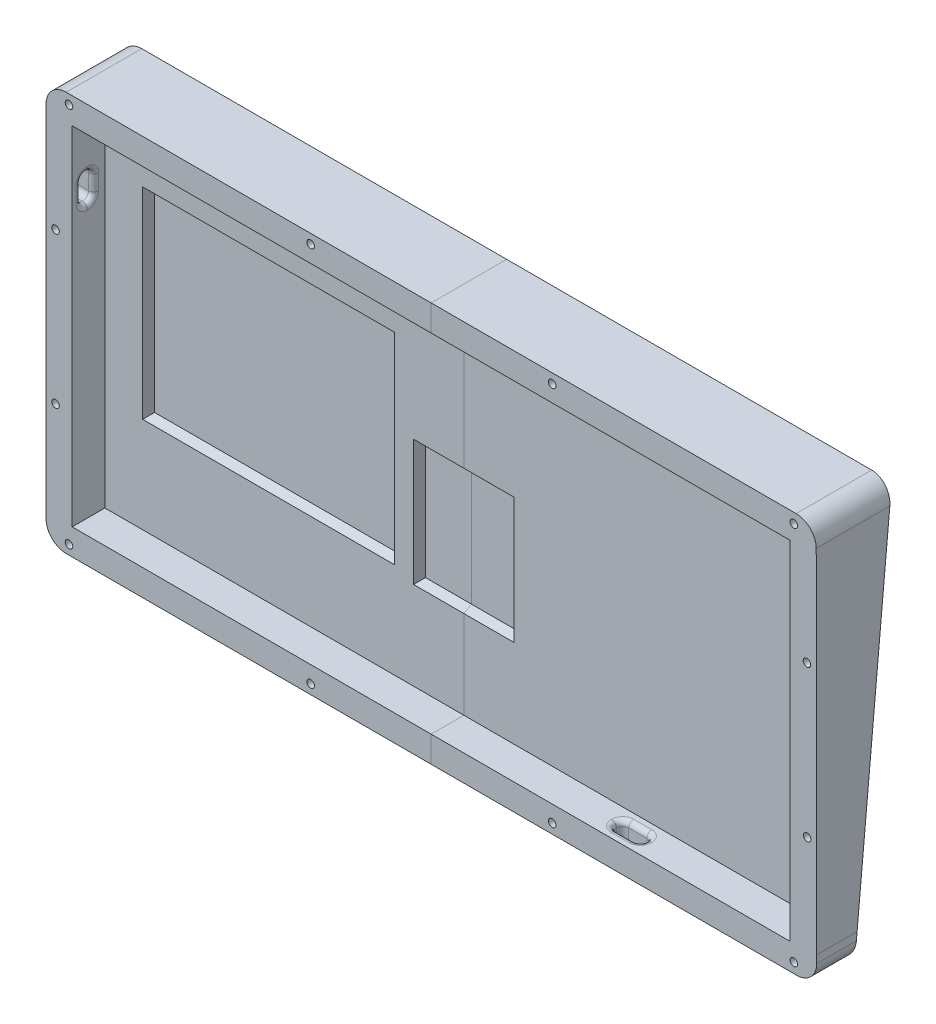
SolidWorks part; units mm, degrees
ref_plane "Front Plane" through (0, 0, 0) normal (0, 0, 1) x (1, 0, 0)
ref_plane "Top Plane" through (0, 0, 0) normal (0, 1, 0) x (1, 0, 0)
ref_plane "Right Plane" through (0, 0, 0) normal (1, 0, 0) x (0, 0, -1)
sketch "Model" plane through (0, 0, 0) normal (0, 0, 1) x (1, 0, 0)
  line L0 (0, 11) -> (0, 150.75)
  line L1 (306.2071, 11.0112) -> (306.0112, 150.7612)
  line L2 (298.0112, 158.75) -> (8, 158.75)
  line L3 (0, 11) -> (0, 8)
  line L4 (8, 0) -> (298.2071, 0)
  line L5 (306.2071, 11.0112) -> (306.2071, 8)
  line L6 (295.63, 10.37) -> (10.37, 10.37)
  line L7 (10.37, 10.37) -> (10.37, 148.38)
  line L8 (10.37, 148.38) -> (295.63, 148.38)
  line L9 (295.63, 148.38) -> (295.63, 10.37)
  arc A0 (8, 158.75) -> (0, 150.75) centre (8, 150.75) ccw
  arc A1 (306.0112, 150.7612) -> (298.0112, 158.75) centre (298.0112, 150.75) ccw
  arc A2 (0, 8) -> (8, 0) centre (8, 8) ccw
  arc A3 (298.2071, 0) -> (306.2071, 8) centre (298.2071, 8) ccw
  circle A4 centre (105.1086, 3.75) radius 1.5
  circle A5 centre (9.1086, 3.75) radius 1.5
  circle A6 centre (201.1085, 3.8173) radius 1.5
  circle A7 centre (297.1084, 3.9518) radius 1.5
  circle A8 centre (105.1086, 155) radius 1.5
  circle A9 centre (9.1086, 155) radius 1.5
  circle A10 centre (201.1085, 154.9327) radius 1.5
  circle A11 centre (297.1084, 154.7982) radius 1.5
  circle A12 centre (3.75, 109.375) radius 1.5
  circle A13 centre (3.75, 49.375) radius 1.5
  circle A14 centre (302.3189, 109.5842) radius 1.5
  circle A15 centre (302.403, 49.5843) radius 1.5
sketch "草图2" plane through (0, 0, 0) normal (0, 0, 1) x (1, 0, 0)
  line L0 (0, 11) -> (0, 150.75)
  line L1 (306.2071, 11.0112) -> (306.0112, 150.7612)
  line L2 (298.0112, 158.75) -> (8, 158.75)
  line L3 (0, 11) -> (0, 8)
  line L4 (8, 0) -> (298.2071, 0)
  line L5 (306.2071, 11.0112) -> (306.2071, 8)
  line L6 (295.63, 10.37) -> (10.37, 10.37)
  line L7 (10.37, 10.37) -> (10.37, 148.38)
  line L8 (10.37, 148.38) -> (295.63, 148.38)
  line L9 (295.63, 148.38) -> (295.63, 10.37)
  arc A0 (8, 158.75) -> (0, 150.75) centre (8, 150.75) ccw
  arc A1 (306.0112, 150.7612) -> (298.0112, 158.75) centre (298.0112, 150.75) ccw
  arc A2 (0, 8) -> (8, 0) centre (8, 8) ccw
  arc A3 (298.2071, 0) -> (306.2071, 8) centre (298.2071, 8) ccw
  circle A4 centre (105.1086, 3.75) radius 1.5
  circle A5 centre (9.1086, 3.75) radius 1.5
  circle A6 centre (201.1085, 3.8173) radius 1.5
  circle A7 centre (297.1084, 3.9518) radius 1.5
  circle A8 centre (105.1086, 155) radius 1.5
  circle A9 centre (9.1086, 155) radius 1.5
  circle A10 centre (201.1085, 154.9327) radius 1.5
  circle A11 centre (297.1084, 154.7982) radius 1.5
  circle A12 centre (3.75, 109.375) radius 1.5
  circle A13 centre (3.75, 49.375) radius 1.5
  circle A14 centre (302.3189, 109.5842) radius 1.5
  circle A15 centre (302.403, 49.5843) radius 1.5
sketch "草图3" plane through (0, 0, 0) normal (0, 0, 1) x (1, 0, 0)
  line L0 (0, 11) -> (0, 150.75)
  line L1 (306.2071, 11.0112) -> (306.0112, 150.7612)
  line L2 (298.0112, 158.75) -> (8, 158.75)
  line L3 (0, 11) -> (0, 8)
  line L4 (8, 0) -> (298.2071, 0)
  line L5 (306.2071, 11.0112) -> (306.2071, 8)
  line L6 (295.63, 10.37) -> (10.37, 10.37)
  line L7 (10.37, 10.37) -> (10.37, 148.38)
  line L8 (10.37, 148.38) -> (295.63, 148.38)
  line L9 (295.63, 148.38) -> (295.63, 10.37)
  arc A0 (8, 158.75) -> (0, 150.75) centre (8, 150.75) ccw
  arc A1 (306.0112, 150.7612) -> (298.0112, 158.75) centre (298.0112, 150.75) ccw
  arc A2 (0, 8) -> (8, 0) centre (8, 8) ccw
  arc A3 (298.2071, 0) -> (306.2071, 8) centre (298.2071, 8) ccw
  circle A4 centre (105.1086, 3.75) radius 1.5
  circle A5 centre (9.1086, 3.75) radius 1.5
  circle A6 centre (201.1085, 3.8173) radius 1.5
  circle A7 centre (297.1084, 3.9518) radius 1.5
  circle A8 centre (105.1086, 155) radius 1.5
  circle A9 centre (9.1086, 155) radius 1.5
  circle A10 centre (201.1085, 154.9327) radius 1.5
  circle A11 centre (297.1084, 154.7982) radius 1.5
  circle A12 centre (3.75, 109.375) radius 1.5
  circle A13 centre (3.75, 49.375) radius 1.5
  circle A14 centre (302.3189, 109.5842) radius 1.5
  circle A15 centre (302.403, 49.5843) radius 1.5
sketch "草图4" plane through (0, 0, 0) normal (0, 0, 1) x (1, 0, 0)
  line L0 (0, 11) -> (0, 150.75)
  line L1 (306.2071, 11.0112) -> (306.0112, 150.7612)
  line L2 (298.0112, 158.75) -> (8, 158.75)
  line L3 (0, 11) -> (0, 8)
  line L4 (8, 0) -> (298.2071, 0)
  line L5 (306.2071, 11.0112) -> (306.2071, 8)
  line L6 (295.63, 10.37) -> (10.37, 10.37)
  line L7 (10.37, 10.37) -> (10.37, 148.38)
  line L8 (10.37, 148.38) -> (295.63, 148.38)
  line L9 (295.63, 148.38) -> (295.63, 10.37)
  arc A0 (8, 158.75) -> (0, 150.75) centre (8, 150.75) ccw
  arc A1 (306.0112, 150.7612) -> (298.0112, 158.75) centre (298.0112, 150.75) ccw
  arc A2 (0, 8) -> (8, 0) centre (8, 8) ccw
  arc A3 (298.2071, 0) -> (306.2071, 8) centre (298.2071, 8) ccw
  circle A4 centre (105.1086, 3.75) radius 1.5
  circle A5 centre (9.1086, 3.75) radius 1.5
  circle A6 centre (201.1085, 3.8173) radius 1.5
  circle A7 centre (297.1084, 3.9518) radius 1.5
  circle A8 centre (105.1086, 155) radius 1.5
  circle A9 centre (9.1086, 155) radius 1.5
  circle A10 centre (201.1085, 154.9327) radius 1.5
  circle A11 centre (297.1084, 154.7982) radius 1.5
  circle A12 centre (3.75, 109.375) radius 1.5
  circle A13 centre (3.75, 49.375) radius 1.5
  circle A14 centre (302.3189, 109.5842) radius 1.5
  circle A15 centre (302.403, 49.5843) radius 1.5
extrude "凸台-拉伸1" add sketch "Model" against normal blind 30 contours L2 A0 L0 L3 A2 L4 A3 L5 L1 A1
extrude "切除-拉伸1" cut sketch "草图2" against normal blind 5 contours A4 | A5 | A10 | A11 | A7 | A6 | A13 | A12 | A8 | A9 | A14 | A15
sketch "草图6" plane through (0, 0, 0) normal (-1, 0, 0) x (0, 0, 1)
  line L0 (-30, 158.75) -> (-30, 0)
  line L1 (-30, 0) -> (-15, 0)
  line L2 (-30, 0) -> (0, 0) construction
  line L3 (-15, 0) -> (-30, 158.75)
extrude "切除-拉伸4" cut sketch "草图6" against normal blind 307 contours L3 L0 L1
extrude "切除-拉伸5" cut sketch "草图3" against normal blind 13 contours L8 L9 L6 L7
sketch "草图8" plane through (0, 0, 0) normal (0, 0, 1) x (1, 0, 0)
  line L0 (10.37, 148.38) -> (10.37, 129.38)
  line L1 (10.37, 10.37) -> (10.37, 148.38) construction
  line L2 (10.37, 129.38) -> (0, 129.38)
  line L3 (0, 11) -> (0, 150.75) construction
  line L4 (0, 129.38) -> (0, 118.38)
  line L5 (0, 118.38) -> (10.37, 118.38)
  line L6 (295.63, 10.37) -> (232.13, 10.37)
  line L7 (295.63, 10.37) -> (10.37, 10.37) construction
  line L8 (232.13, 10.37) -> (232.13, 0)
  line L9 (8, 0) -> (298.2071, 0) construction
  line L10 (232.13, 0) -> (220.13, 0)
  line L11 (220.13, 0) -> (220.13, 10.37)
  line L12 (220.13, 10.37) -> (232.13, 10.37)
  line L13 (10.37, 118.38) -> (10.37, 129.38)
sketch "草图9" plane through (0, 0, -13) normal (0, 0, 1) x (1, 0, 0)
  line L5 (25.37, 128.38) -> (125.37, 128.38)
  line L6 (25.37, 128.38) -> (25.37, 48.38)
  line L7 (25.37, 48.38) -> (125.37, 48.38)
  line L8 (125.37, 128.38) -> (125.37, 48.38)
sketch "草图12" plane through (0, 0, -13) normal (0, 0, 1) x (1, 0, 0)
  line L11 (133, 45.37) -> (173, 45.37)
  line L12 (133, 45.37) -> (133, 95.37)
  line L13 (133, 95.37) -> (173, 95.37)
  line L14 (173, 45.37) -> (173, 95.37)
extrude "切除-拉伸7" cut sketch "草图12" against normal blind 3 draft 30
extrude "切除-拉伸8" cut sketch "草图9" against normal blind 3 draft 30 contours L5 L8 L7 L6
sketch "草图14" plane through (0, 0, 0) normal (-1, 0, 0) x (0, 0, 1)
  line L6 (-5.9, 129.38) -> (-6.1, 129.38)
  line L7 (-3.5, 126.98) -> (-3.5, 120.78)
  line L8 (-5.9, 118.38) -> (-6.1, 118.38)
  line L9 (-8.5, 126.98) -> (-8.5, 120.78)
  arc A0 (-6.1, 118.38) -> (-8.5, 120.78) centre (-6.1, 120.78) cw
  arc A1 (-5.9, 118.38) -> (-3.5, 120.78) centre (-5.9, 120.78) ccw
  arc A2 (-3.5, 126.98) -> (-5.9, 129.38) centre (-5.9, 126.98) ccw
  arc A3 (-8.5, 126.98) -> (-6.1, 129.38) centre (-6.1, 126.98) cw
  point P12 (0, 0)
  dimension "D1" = 2.4
extrude "切除-拉伸9" cut sketch "草图14" against normal blind 11 contours L7 A1 L8 A0 L9 A3 L6 A2
fillet "圆角1" radius 2 8 edges at (0, 128.6771, -7.7971) (0, 129.38, -6) (0, 128.6771, -4.2029) (0, 123.88, -3.5) (0, 119.0829, -4.2029) (0, 118.38, -6) (0, 119.0829, -7.7971) (0, 123.88, -8.5)
sketch "草图15" plane through (0, 0, 0) normal (0, -1, 0) x (1, 0, 0)
  line L6 (222.53, -3.9597) -> (229.73, -3.9597)
  line L7 (220.13, -6.3597) -> (220.13, -6.5597)
  line L8 (222.53, -8.9597) -> (229.73, -8.9597)
  line L9 (232.13, -6.3597) -> (232.13, -6.5597)
  arc A0 (220.13, -6.5597) -> (222.53, -8.9597) centre (222.53, -6.5597) ccw
  arc A1 (232.13, -6.5597) -> (229.73, -8.9597) centre (229.73, -6.5597) cw
  arc A2 (232.13, -6.3597) -> (229.73, -3.9597) centre (229.73, -6.3597) ccw
  arc A3 (222.53, -3.9597) -> (220.13, -6.3597) centre (222.53, -6.3597) ccw
  dimension "D1" = 2.4
extrude "切除-拉伸10" cut sketch "草图15" against normal blind 11 contours L6 A2 L9 A1 L8 A0 L7 A3
fillet "圆角2" radius 2 8 edges at (232.13, 0, -6.4597) (231.4271, 0, -4.6626) (226.13, 0, -3.9597) (220.8329, 0, -4.6626) (220.13, 0, -6.4597) (220.8329, 0, -8.2567) (226.13, 0, -8.9597) (231.4271, 0, -8.2567)
fillet "圆角3" radius 2 8 edges at (10.37, 129.38, -6) (10.37, 128.6771, -4.2029) (10.37, 123.88, -3.5) (10.37, 119.0829, -4.2029) (10.37, 118.38, -6) (10.37, 119.0829, -7.7971) (10.37, 123.88, -8.5) (10.37, 128.6771, -7.7971)
fillet "圆角4" radius 2 8 edges at (231.4271, 10.37, -8.2567) (232.13, 10.37, -6.4597) (231.4271, 10.37, -4.6626) (226.13, 10.37, -3.9597) (220.8329, 10.37, -4.6626) (220.13, 10.37, -6.4597) (220.8329, 10.37, -8.2567) (226.13, 10.37, -8.9597)
sketch "草图17" plane through (0, 158.75, 0) normal (0, 1, 0) x (1, 0, 0)
  line L0 (153.0056, 30) -> (153.0056, 0)
  line L1 (298.0112, 30) -> (8, 30) construction
  line L2 (298.0112, 0) -> (8, 0) construction
sketch "草图18" plane through (0, 0, 0) normal (0, -1, 0) x (1, 0, 0)
  line L0 (153.0056, 0) -> (153.0056, -15)
  line L1 (153.0056, -30) -> (153.0056, 0) construction
ref_plane "基准面1" through (153.0056, 0, 0) normal (1, 0, 0) x (0, 0, -1)
split "分割1" trim tools "基准面1" bodies to split 111 resulting bodies 112 113
